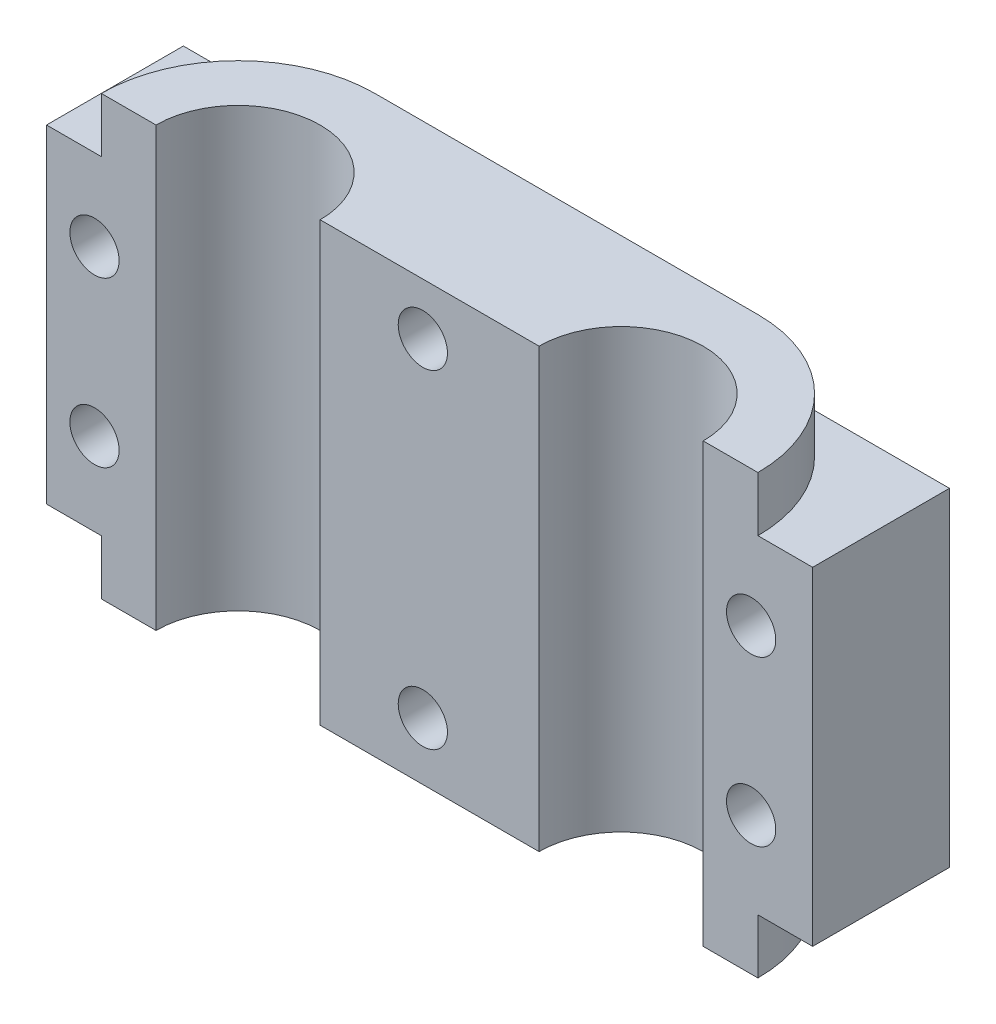
SolidWorks part; units mm, degrees
ref_plane "Front Plane" through (0, 0, 0) normal (0, 0, 1) x (1, 0, 0)
ref_plane "Top Plane" through (0, 0, 0) normal (0, 1, 0) x (1, 0, 0)
ref_plane "Right Plane" through (0, 0, 0) normal (1, 0, 0) x (0, 0, -1)
sketch "Sketch1" plane through (0, 0, 0) normal (0, 1, 0) x (1, 0, 0)
  line L0 (-67.8947, 0) -> (53.4868, 0) construction
  line L1 (0, 36.0197) -> (0, -28.7171) construction
  line L2 (10, 0) -> (-10, 0)
  line L3 (-25, 0) -> (-35, 0)
  line L4 (-35, 0) -> (-35, 12.5)
  line L5 (-35, 12.5) -> (0, 12.5)
  line L6 (25, 0) -> (35, 0)
  line L7 (35, 0) -> (35, 12.5)
  line L8 (35, 12.5) -> (0, 12.5)
  arc A0 (-10, 0) -> (-25, 0) centre (-17.5, 0) ccw
  arc A1 (-30, 0) -> (-17.5, 12.5) centre (-17.5, 0) cw
  arc A2 (10, 0) -> (25, 0) centre (17.5, 0) cw
  arc A3 (30, 0) -> (17.5, 12.5) centre (17.5, 0) ccw
  point P17 (0, 0)
  dimension "D1" = 7.5
  dimension "D5" = 12.5
  dimension "D6" = 12.5
  dimension "D2" = 17.5
  dimension "D3" = 12.5
  dimension "D4" = 70
extrude "Boss-Extrude1" add sketch "Sketch1" along normal mid plane 40 contours L6 A3 L8 L5 A1 L3 A0 L2 A2 region at (0, 0, -6.8625)
extrude "Boss-Extrude2" add sketch "Sketch1<3>" along normal mid plane 30 contours L3 A1 L5 L4 | A3 L6 L7 L8 region at (30.6521, 0, -7.4574) region at (-30.6521, 0, -7.4574)
sketch "Sketch1<3>" plane through (0, 0, 0) normal (0, 1, 0) x (1, 0, 0) same geometry as "Sketch1"
hole_wizard "Ø1.0mm Dowel Hole1" positions "Sketch4" profile "Sketch5" hole size "Ø1.0" standard "ANSI Metric"
sketch "Sketch4" plane through (0, 0, -12.5) normal (0, 0, -1) x (-1, 0, 0)
  line L0 (35, 0) -> (-35, 0) construction
  line L1 (35, 15) -> (35, -15) construction
  line L2 (-35, 15) -> (-35, -15) construction
  line L3 (0, -20) -> (0, 20) construction
  line L4 (-17.5, -20) -> (17.5, -20) construction
  line L5 (-17.5, 20) -> (17.5, 20) construction
  point P0 (0.6188, -14.7359)
  point P2 (-29.3812, -7.429)
  point P4 (30.6188, -7.429)
  point P6 (30.6188, 7.571)
  point P8 (0.6188, 15.2641)
  point P10 (-29.3812, 7.571)
  dimension "D1" = 15
  dimension "D2" = 30
  dimension "D3" = 30
  dimension "D4" = 30
sketch "Sketch5" plane through (-0.6188, -14.7359, -12.5) normal (1, 0, 0) x (0, 1, 0)
  line L0 (0, 0) -> (0, 16.299)
  line L1 (0, 16.299) -> (2.25, 15)
  line L2 (2.25, 15) -> (2.25, 0)
  line L5 (2.25, 0) -> (0, 0)
  line L10 (0, 16.299) -> (-2.25, 15) construction
  line L11 (0, -6.35) -> (0, 107.95) construction
  dimension "Hole Dia." = 4.5
  dimension "Hole Depth" = 15
  dimension "Drill Angle" = 120
